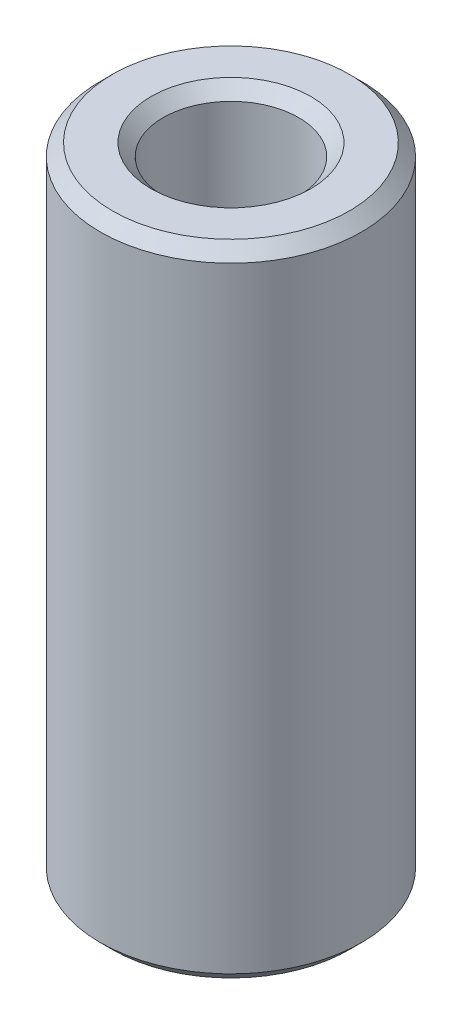
SolidWorks part; units mm, degrees
ref_plane "Front Plane" through (0, 0, 0) normal (0, 0, 1) x (1, 0, 0)
ref_plane "Top Plane" through (0, 0, 0) normal (0, 1, 0) x (1, 0, 0)
ref_plane "Right Plane" through (0, 0, 0) normal (1, 0, 0) x (0, 0, -1)
sketch "Sketch1" plane through (0, 0, 0) normal (0, 1, 0) x (1, 0, 0)
  circle A0 centre (0, 0) radius 30
  dimension "SLEEVE_OD" = 60
extrude "Boss-Extrude1" add sketch "Sketch1" along normal blind 146.9868
sketch "Sketch2" plane through (0, 0, 0) normal (0, 1, 0) x (1, 0, 0)
  circle A0 centre (0, 0) radius 15.5687
  dimension "BORE_D" = 31.1373
extrude "Cut-Extrude1" cut sketch "Sketch2" along normal through all
chamfer "Chamfer1" distance 2.7952 angle 45 4 edges at (0, 146.9868, 15.5687) (0, 0, 15.5687) (0, 0, 30) (0, 146.9868, 30)
